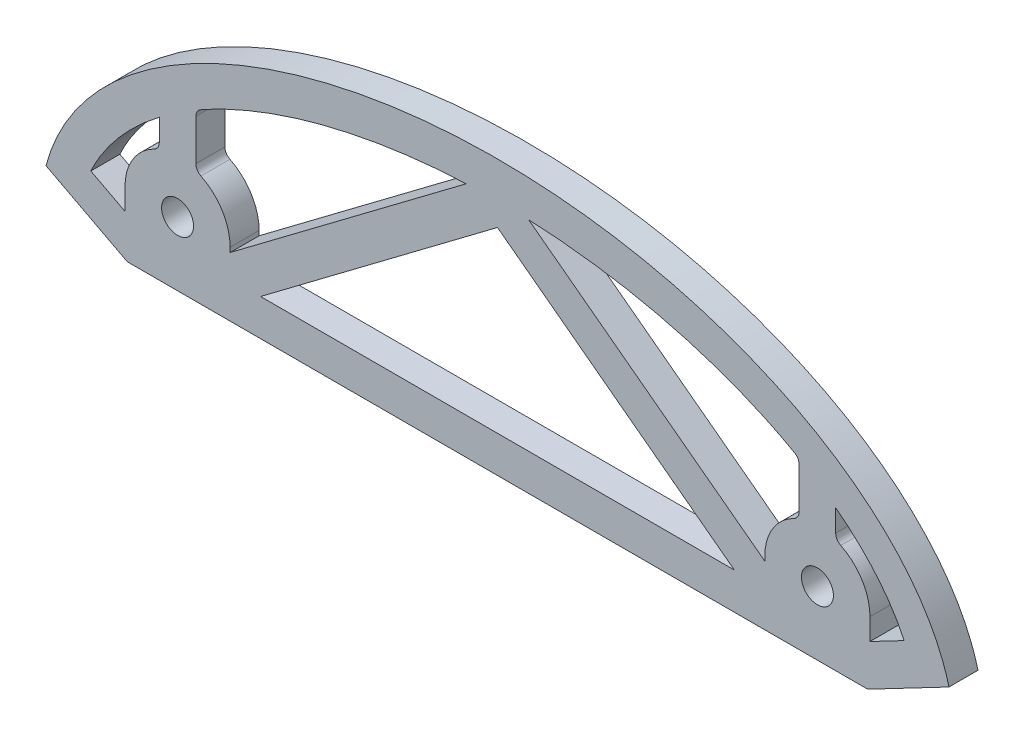
SolidWorks part; units mm, degrees
material "Mahogany"
ref_plane "Front Plane" through (0, 0, 0) normal (0, 0, 1) x (1, 0, 0)
ref_plane "Top Plane" through (0, 0, 0) normal (0, 1, 0) x (1, 0, 0)
ref_plane "Right Plane" through (0, 0, 0) normal (1, 0, 0) x (0, 0, -1)
sketch "Sketch1" plane through (0, 0, 0) normal (0, 0, 1) x (1, 0, 0)
  line L0 (50, 30) -> (50, 0) construction
  line L1 (0, 0) -> (100, 0) construction
  line L2 (0, 0) -> (0, 30) construction
  line L3 (0, 30) -> (100, 30) construction
  line L4 (100, 0) -> (100, 30) construction
  line L5 (9.5, 12) -> (20.5, 12) construction
  line L6 (9.5, 12) -> (9.5, 0) construction
  line L7 (9.5, 0) -> (20.5, 0) construction
  line L8 (20.5, 12) -> (20.5, 0) construction
  line L9 (15, 0) -> (15, 7) construction
  line L10 (85, 0) -> (85, 7) construction
  line L11 (79.5, 12) -> (79.5, 0) construction
  line L12 (90.5, 0) -> (79.5, 0) construction
  line L13 (90.5, 12) -> (90.5, 0) construction
  line L14 (90.5, 12) -> (79.5, 12) construction
  line L15 (9.5, 0) -> (0.606, 4.6564)
  line L16 (9.5, 0) -> (50, 0)
  line L17 (50, 30) -> (50, 26) construction
  line L18 (20.75, 4) -> (79.25, 4)
  line L19 (20.75, 4) -> (50, 26) construction
  line L20 (9.25, 12.0623) -> (9.25, 4.6459)
  line L21 (20.75, 20.0667) -> (20.75, 4)
  line L22 (10.4837, 4) -> (2.4612, 8.2001) construction
  line L23 (13.25, 7) -> (13.25, 15.6376) construction
  line L24 (16.75, 7) -> (16.75, 17.9668) construction
  line L25 (9.25, 4.6459) -> (5.5089, 6.6046)
  line L26 (10.4837, 4) -> (50, 4) construction
  line L27 (20.75, 6.5026) -> (46.5769, 25.9279)
  line L28 (50, 23.4974) -> (24.0773, 4)
  line L29 (90.5, 0) -> (99.394, 4.6564)
  line L30 (90.5, 0) -> (50, 0)
  line L31 (50, 23.4974) -> (75.9227, 4)
  line L32 (79.25, 6.5026) -> (53.4231, 25.9279)
  line L33 (79.25, 20.0667) -> (79.25, 4)
  line L34 (90.75, 12.0623) -> (90.75, 4.6459)
  line L35 (90.75, 4.6459) -> (94.4911, 6.6046)
  circle A0 centre (15, 7) radius 1.75
  circle A1 centre (85, 7) radius 1.75
  circle A2 centre (85, 7) radius 1.75
  ellipse E0 centre (50, 0) end of major axis (0, 0) minor radius 30 (0, 0) -> (100, 0) cw
  ellipse E1 centre (50, 0) end of major axis (96, 0) minor radius 26 (94.4911, 6.6046) -> (90.75, 12.0623) ccw
  ellipse E2 centre (50, 0) end of major axis (96, 0) minor radius 26 (4.2571, 2.7449) -> (4, 0) ccw
  ellipse E3 centre (50, 0) end of major axis (96, 0) minor radius 26 (9.25, 12.0623) -> (5.5089, 6.6046) ccw
  ellipse E4 centre (50, 0) end of major axis (96, 0) minor radius 26 (79.25, 20.0667) -> (20.75, 20.0667) ccw
  point P71 (5.053, 2.3282)
  dimension "D6" = 3.5
  dimension "D1" = 30
  dimension "D2" = 100
  dimension "D3" = 12
  dimension "D4" = 7
  dimension "D5" = 11
  dimension "D7" = 70
  dimension "D8" = 4
  dimension "D9" = 4
  dimension "D11" = 4
  dimension "D12" = 4
  dimension "D13" = 2
  dimension "D14" = 2
  dimension "D15" = 4
  dimension "D10" = 4
extrude "Boss-Extrude1" add sketch "Sketch1" along normal blind 3.175 contours E0 L15 L16 L30 L29 E4 L33 L18 L21 E3 L20 L25 E1 L35 L34 A0 A1 | L32 E4 L27 L21 L18 L28 L31 L33 region at (7.3574, 2.2871, 0) region at (21.375, 5.2513, 0)
sketch "Sketch2" plane through (0, 0, 3.175) normal (0, 0, 1) x (1, 0, 0)
  line L0 (9.25, 4.6459) -> (9.25, 17.3838) construction
  line L1 (20.75, 7) -> (21.5, 20.4086)
  line L2 (9.25, 12.0623) -> (9.25, 7)
  line L3 (15, 7) -> (15, 16.8715) construction
  line L4 (13, 15.4481) -> (13, 13.0467)
  line L5 (17, 17.5339) -> (17, 13.0467)
  line L6 (50, 26) -> (50, 4) construction
  line L7 (24.0773, 4) -> (75.9227, 4) construction
  line L8 (85, 7) -> (85, 16.8715) construction
  line L9 (90.75, 4.6459) -> (90.75, 17.3838) construction
  line L10 (83, 17.5339) -> (83, 13.0467)
  line L11 (87, 15.4481) -> (87, 13.0467)
  line L12 (90.75, 12.0623) -> (90.75, 7)
  line L13 (79.25, 7) -> (78.5, 20.4086)
  arc A0 (12.4444, 12.1509) -> (9.25, 7) centre (15, 7) ccw
  arc A1 (20.75, 7) -> (17.5556, 12.1509) centre (15, 7) ccw
  circle A2 centre (15, 7) radius 1.75 construction
  arc A3 (17, 17.5339) -> (17.5088, 18.4049) centre (18, 17.5339) cw
  arc A4 (17, 13.0467) -> (17.5556, 12.1509) centre (18, 13.0467) ccw
  arc A5 (13, 13.0467) -> (12.4444, 12.1509) centre (12, 13.0467) cw
  arc A6 (87, 13.0467) -> (87.5556, 12.1509) centre (88, 13.0467) ccw
  arc A7 (83, 13.0467) -> (82.4444, 12.1509) centre (82, 13.0467) cw
  arc A8 (83, 17.5339) -> (82.4912, 18.4049) centre (82, 17.5339) ccw
  arc A9 (79.25, 7) -> (82.4444, 12.1509) centre (85, 7) cw
  arc A10 (87.5556, 12.1509) -> (90.75, 7) centre (85, 7) cw
  ellipse E0 centre (50, 0) end of major axis (4, 0) minor radius 26 (46.5769, 25.9279) -> (20.75, 20.0667) ccw construction
  ellipse E1 centre (50, 0) end of major axis (4, 0) minor radius 26 (46.5769, 25.9279) -> (17.5088, 18.4049) ccw
  ellipse E2 centre (50, 0) end of major axis (0, 0) minor radius 30 (99.394, 4.6564) -> (0.606, 4.6564) ccw construction
  ellipse E3 centre (50, 0) end of major axis (4, 0) minor radius 26 (13, 15.4481) -> (9.25, 12.0623) ccw
  ellipse E4 centre (50, 0) end of major axis (4, 0) minor radius 26 (53.4231, 25.9279) -> (82.4912, 18.4049) cw
  ellipse E5 centre (50, 0) end of major axis (4, 0) minor radius 26 (87, 15.4481) -> (90.75, 12.0623) cw
  point P44 (13, 12.391)
  point P76 (87, 12.391)
  line M8 (20.75, 6.5026) -> (20.75, 20.0667)
  line M12 (79.25, 20.0667) -> (79.25, 6.5026)
  line M16 (9.25, 12.0623) -> (9.25, 4.6459)
  line M20 (90.75, 4.6459) -> (90.75, 12.0623)
  dimension "D4" = 1
  dimension "D1" = 4
  dimension "D2" = 2
  dimension "D3" = 2
extrude "Cut-Extrude2" cut sketch "Sketch2" against normal through all both contours E1 A3 L5 A4 A1 M8 | L4 E3 A0 A5 M16 | E4 A9 A7 L10 A8 M12 | E5 L11 A6 A10 M20 region at (19.1119, 14.9517, 3.175) region at (11.0402, 12.2909, 3.175) region at (80.8881, 14.9517, 3.175) region at (88.9598, 12.2909, 3.175)
equation "\"prop-dist\"= 70mm"
equation "\"prop-hole-depth\"= 9mm"
equation "\"prop-hole-diameter\"= 11mm"
equation "\"rivet-extension\" = 12mm"
equation "\"rivet-hole-extension\"= 7mm"
equation "\"rivet-hole-diameter\"= 3.5mm"
equation "\"ski-length\"= 100mm"
equation "\"th\"= 0.125in'material thickness"
equation "\"ski-height\"= 30mm"
equation "\"ski-curve-gap\"= 60mm"
equation "\"ski-curve-height\"= \"rivet-hole-extension\""
equation "\"min-width\"= 4mm"
equation "\"D1@Sketch1\"=\"ski-height\""
equation "\"D2@Sketch1\"=\"ski-length\""
equation "\"D3@Sketch1\"=\"rivet-extension\""
equation "\"D4@Sketch1\"=\"rivet-hole-extension\""
equation "\"D5@Sketch1\"=\"prop-hole-diameter\""
equation "\"D6@Sketch1\"=\"rivet-hole-diameter\""
equation "\"D7@Sketch1\"=\"prop-dist\""
equation "\"D9@Sketch1\"=\"min-width\""
equation "\"D11@Sketch1\"=\"min-width\""
equation "\"D12@Sketch1\"=\"min-width\""
equation "\"D13@Sketch1\"=\"min-width\"/2"
equation "\"D14@Sketch1\"=\"min-width\"/2"
equation "\"D1@Boss-Extrude1\"=\"th\""
equation "\"D15@Sketch1\"=\"min-width\""
equation "\"D1@Sketch2\"=\"min-width\""
equation "\"D2@Sketch2\"=\"min-width\"/2"
equation "\"D3@Sketch2\"=\"min-width\"/2"
